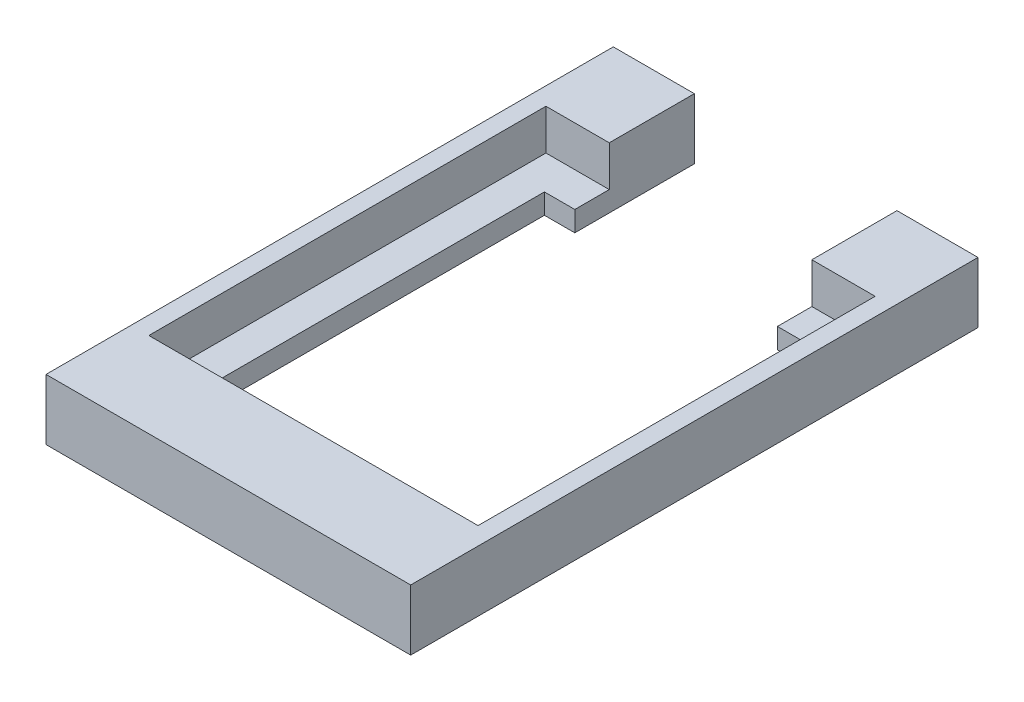
SolidWorks part; units mm, degrees
ref_plane "Front Plane" through (0, 0, 0) normal (0, 0, 1) x (1, 0, 0)
ref_plane "Top Plane" through (0, 0, 0) normal (0, 1, 0) x (1, 0, 0)
ref_plane "Right Plane" through (0, 0, 0) normal (1, 0, 0) x (0, 0, -1)
sketch "Sketch1" plane through (0, 0, 0) normal (0, 1, 0) x (1, 0, 0)
  line L1 (-6.5, -8.1) -> (6.5, -8.1)
  line L2 (-6.5, -8.1) -> (-6.5, 8.1)
  line L3 (-6.5, 8.1) -> (6.5, 8.1)
  line L4 (6.5, -8.1) -> (6.5, 8.1)
  line L5 (-6.5, -8.1) -> (6.5, 8.1) construction
  line L6 (-6.5, 8.1) -> (6.5, -8.1) construction
  line L7 (-9, -14) -> (9, -14)
  line L8 (-9, -14) -> (-9, 14)
  line L9 (-9, 14) -> (9, 14)
  line L10 (9, -14) -> (9, 14)
  line L11 (-9, -14) -> (9, 14) construction
  line L12 (-9, 14) -> (9, -14) construction
  point P0 (0, 0)
  point P6 (0, 0)
  dimension "D1" = 16.2
  dimension "D2" = 13
  dimension "D3" = 18
  dimension "D4" = 28
extrude "Boss-Extrude1" add sketch "Sketch1" along normal blind 3 contours L1 L4 L3 L2 | L7 L10 L9 L8 L4 L1 L2 L3 region at (0, 0, 0) region at (-8.6671, 0, 0)
extrude "Cut-Extrude1" cut sketch "Sketch1<3>" along normal through all contours L1 L4 L3 L2 region at (0, 0, 0)
sketch "Sketch1<3>" plane through (0, 0, 0) normal (0, 1, 0) x (1, 0, 0) same geometry as "Sketch1"
sketch "Sketch2" plane through (0, 3, 0) normal (0, 1, 0) x (1, 0, 0)
  line L1 (8.125, -9.8) -> (-8.125, -9.8)
  line L2 (8.125, -9.8) -> (8.125, 9.8)
  line L3 (8.125, 9.8) -> (-8.125, 9.8)
  line L4 (-8.125, -9.8) -> (-8.125, 9.8)
  line L5 (8.125, -9.8) -> (-8.125, 9.8) construction
  line L6 (8.125, 9.8) -> (-8.125, -9.8) construction
  point P0 (0, 0)
  dimension "D1" = 19.6
  dimension "D2" = 16.25
extrude "Cut-Extrude2" cut sketch "Sketch2" against normal blind 2
sketch "Sketch4" plane through (0, 3, 0) normal (0, 1, 0) x (1, 0, 0)
  line L0 (0, 0) -> (0, 14) construction
  line L1 (-9, 14) -> (9, 14) construction
  line L2 (8.125, 9.8) -> (-8.125, 9.8) construction
  line L3 (5, 5.3) -> (-5, 5.3)
  line L4 (5, 5.3) -> (5, 14.3)
  line L5 (5, 14.3) -> (-5, 14.3)
  line L6 (-5, 5.3) -> (-5, 14.3)
  line L7 (5, 5.3) -> (-5, 14.3) construction
  line L8 (5, 14.3) -> (-5, 5.3) construction
  point P5 (0, 9.8)
  dimension "D1" = 10
  dimension "D2" = 9
extrude "Cut-Extrude3" cut sketch "Sketch4" against normal through all
